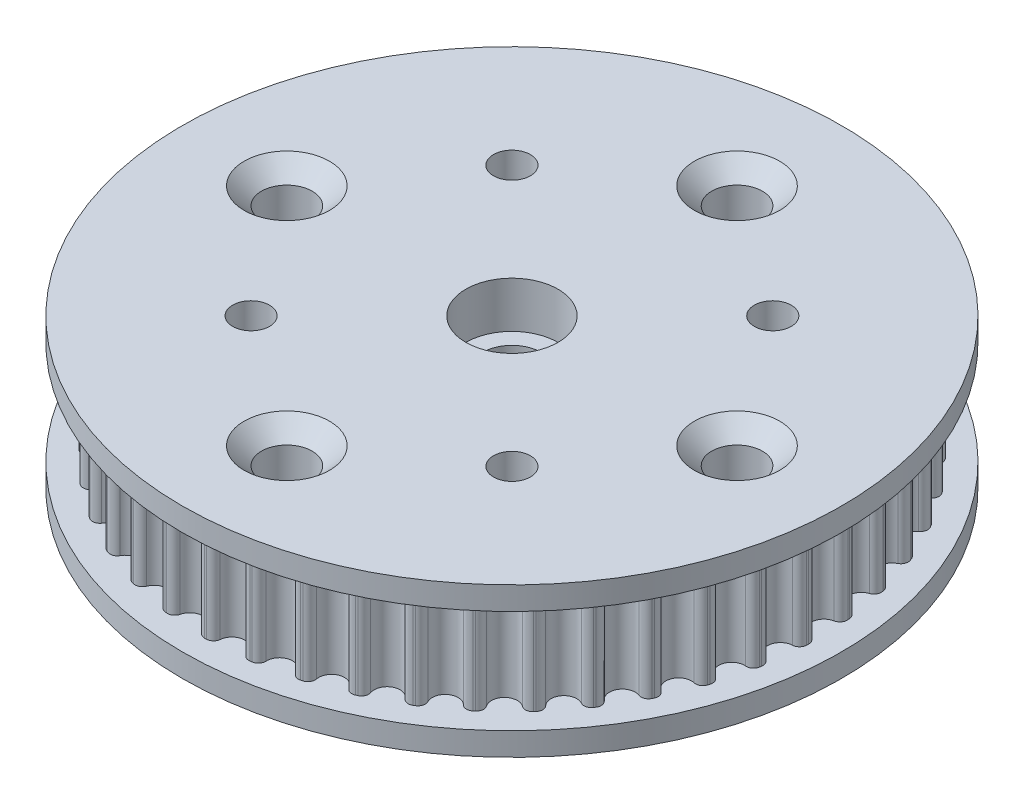
SolidWorks part; units mm, degrees
ref_plane "Front Plane" through (0, 0, 0) normal (0, 0, 1) x (1, 0, 0)
ref_plane "Top Plane" through (0, 0, 0) normal (0, 1, 0) x (1, 0, 0)
ref_plane "Right Plane" through (0, 0, 0) normal (1, 0, 0) x (0, 0, -1)
sketch "Sketch1" plane through (0, 0, 0) normal (0, 1, 0) x (1, 0, 0)
  line L0 (0, 0) -> (0, 21.1048) construction
  line L1 (0, 0) -> (2.8913, 20.5726) construction
  circle A0 centre (0, 0) radius 21.1048 construction
  circle A1 centre (0, 0) radius 19.8848 construction
  circle A2 centre (0, 20.7748) radius 0.89 construction
  circle A5 centre (2.8913, 20.5726) radius 0.89 construction
  arc A6 (0, 19.8848) -> (0.8792, 20.6366) centre (0, 20.7748) ccw
  arc A7 (0.8792, 20.6366) -> (1.4065, 21.0579) centre (1.3731, 20.559) cw
  arc A8 (1.5379, 21.0487) -> (2.0014, 20.5582) centre (1.5015, 20.55) cw
  arc A9 (2.7674, 19.6913) -> (2.0014, 20.5582) centre (2.8913, 20.5726) cw
  arc A10 (1.4065, 21.0579) -> (1.5379, 21.0487) centre (0, 0) cw
  arc A11 (0, 19.8848) -> (2.7674, 19.6913) centre (0, 0) ccw
  dimension "D1" = 42.2096
  dimension "D3" = 1.78
  dimension "D4" = 0.5
  dimension "D2" = 1.22
  dimension "D5" = 8
extrude "Boss-Extrude1" add sketch "Sketch1" along normal mid plane 7.112
ref_axis "Axis1" through (0, 3.3, 0) along (0, -1, 0)
pattern_circular "CirPattern1" count 45 over 360 about axis through (0, 3.3, 0) along (0, -1, 0) of "Boss-Extrude1"
sketch "Sketch2" plane through (0, 0, 0) normal (1, 0, 0) x (0, 0, -1)
  line L0 (-20.6477, 3.556) -> (-21.1047, 3.556) construction
  line L4 (22.6922, 5.1435) -> (2, 5.1435)
  line L5 (22.6922, 5.1435) -> (22.6922, 3.556)
  line L6 (-22.6922, 3.556) -> (22.6922, 3.556) construction
  line L7 (-22.6922, 3.556) -> (-22.6922, 5.1435) construction
  line L8 (-22.6922, 5.1435) -> (22.6922, 5.1435) construction
  line L9 (22.6922, 3.556) -> (22.6922, 5.1435) construction
  line L10 (-22.6922, 3.556) -> (22.6922, 5.1435) construction
  line L11 (-22.6922, 5.1435) -> (22.6922, 3.556) construction
  line L12 (-21.1047, 3.556) -> (-21.1047, -3.556) construction
  line L13 (0, 3.3) -> (0, -3.3) construction
  line L14 (2, 5.1435) -> (2, 3.556)
  line L16 (22.6922, 3.556) -> (2, 3.556)
  line L17 (2, 5.1435) -> (2, 3.556)
  point P0 (0, 4.3498)
  dimension "D1" = 1.5875
  dimension "D2" = 1.5875
  dimension "D3" = 2
revolve "Revolve3" add sketch "Sketch2" angle 360 about axis through (0, 3.3, 0) along (0, -1, 0) region at (0, 4.3497, -12.3461)
mirror "Mirror1" about plane through (0, 0, 0) normal (0, 1, 0) of "Revolve3"
sketch "Sketch3" plane through (0, 3.556, 0) normal (0, 1, 0) x (1, 0, 0)
  line L1 (-8.9803, -8.9803) -> (8.9803, -8.9803) construction
  line L2 (-8.9803, -8.9803) -> (-8.9803, 8.9803) construction
  line L3 (-8.9803, 8.9803) -> (8.9803, 8.9803) construction
  line L4 (8.9803, -8.9803) -> (8.9803, 8.9803) construction
  line L5 (-8.9803, -8.9803) -> (8.9803, 8.9803) construction
  line L6 (-8.9803, 8.9803) -> (8.9803, -8.9803) construction
  circle A0 centre (-15.5, 0) radius 1.7462
  circle A1 centre (0, 0) radius 2
  circle A2 centre (0, 0) radius 2
  circle A3 centre (0, 15.5) radius 1.7462
  circle A4 centre (15.5, 0) radius 1.7462
  circle A5 centre (0, -15.5) radius 1.7462
  circle A6 centre (-8.9803, 8.9803) radius 1.27
  circle A7 centre (8.9803, 8.9803) radius 1.27
  circle A8 centre (8.9803, -8.9803) radius 1.27
  circle A9 centre (-8.9803, -8.9803) radius 1.27
  point P14 (0, 0)
  dimension "D3" = 3.4925
  dimension "D5" = 2.54
  dimension "D2" = 15.5
  dimension "D6" = 25.4
  dimension "D1" = 0
  dimension "D4" = 4
extrude "Cut-Extrude1" cut sketch "Sketch3" against normal through all both and the other way through all
sketch "Sketch4" plane through (0, 5.1435, 0) normal (0, 1, 0) x (1, 0, 0)
  line L0 (-7.9375, 0) -> (7.9375, 0) construction
  line L1 (-7.9375, 3.302) -> (7.9375, 3.302)
  line L2 (-7.9375, -3.302) -> (7.9375, -3.302)
  arc A0 (-7.9375, 3.302) -> (-7.9375, -3.302) centre (-7.9375, 0) ccw
  arc A1 (7.9375, -3.302) -> (7.9375, 3.302) centre (7.9375, 0) ccw
  point P3 (0, 0)
  dimension "D1" = 15.875
  dimension "D2" = 6.604
extrude "Cut-Extrude2" [suppressed] cut sketch "Sketch4" against normal blind 3.175
sketch "Sketch5" [suppressed] plane through (0, 1.9685, 0) normal (0, 1, 0) x (1, 0, 0)
  circle A0 centre (-7.9375, 0) radius 1
  circle A1 centre (7.9375, 0) radius 1
  dimension "D1" = 2
extrude "Cut-Extrude3" [suppressed] cut sketch "Sketch5" against normal through all
ref_axis "Axis2" through (-15.5, -5.1435, 0) along (0, 1, 0)
sketch "Sketch6" plane through (0, 0, 0) normal (0, 0, 1) x (1, 0, 0)
  line L0 (-18.4375, 5.1435) -> (-12.5625, 5.1435) construction
  line L1 (22.6922, 5.1435) -> (-22.6922, 5.1435) construction
  line L2 (-12.5625, 5.1435) -> (-15.5, 2.206)
  line L3 (-15.5, 2.206) -> (-18.4375, 5.1435) construction
  line L4 (-13.7538, 5.1435) -> (-17.2462, 5.1435) construction
  line L5 (-17.2462, 4.8895) -> (-13.7538, 4.8895) construction
  line L6 (-17.2462, 5.1435) -> (-17.2462, -5.1435) construction
  line L7 (-13.7538, -5.1435) -> (-13.7538, 5.1435) construction
  line L8 (-15.5, 2.206) -> (-15.5, 5.1435)
  line L9 (-15.5, 5.1435) -> (-12.5625, 5.1435)
  line L10 (-15.5, -5.1435) -> (-15.5, 5.1435) construction
  point P4 (-15.5, 4.8895)
  point P6 (-15.5, 5.1435)
  dimension "D2" = 5.875
  dimension "D3" = 0.254
revolve "Cut-Revolve2" cut sketch "Sketch6" angle 360 about axis through (-15.5, -5.1435, 0) along (0, 1, 0)
pattern_circular "CirPattern2" count 4 over 360 about axis through (0, 3.3, 0) along (0, -1, 0) of "Cut-Revolve2"
sketch "Sketch7" [suppressed] plane through (0, -5.1435, 0) normal (0, -1, 0) x (-1, 0, 0)
  line L0 (7.9375, 0) -> (-7.9375, 0) construction
  line L1 (7.9375, -2.54) -> (-7.9375, -2.54)
  line L2 (7.9375, 2.54) -> (-7.9375, 2.54)
  arc A0 (7.9375, -2.54) -> (7.9375, 2.54) centre (7.9375, 0) ccw
  arc A1 (-7.9375, 2.54) -> (-7.9375, -2.54) centre (-7.9375, 0) ccw
  point P4 (0, 0)
  dimension "D1" = 5.08
extrude "Cut-Extrude5" [suppressed] cut sketch "Sketch7" against normal offset from surface (2.287 mm away) 8 up to face at (-2.9375, 5.1435, 15.5)
sketch "Sketch8" plane through (0, 5.1435, 0) normal (0, 1, 0) x (1, 0, 0)
  circle A0 centre (0, 0) radius 3.175
  dimension "D1" = 6.35
extrude "Cut-Extrude6" cut sketch "Sketch8" against normal blind 3.175
equation "\"TEETH_NUM\"= 45"
equation "\"TOOTH_PITCH\"= 3mm"
equation "\"PITCH_LINE_OFFSET\"= .015in"
equation "\"DIAMETER_PER_GROOVE\"= .954925mm"
equation "\"PITCH_DIAMETER\"= \"TEETH_NUM\" * \"DIAMETER_PER_GROOVE\""
equation "\"OUTSIDE_DIAMETER\"= \"PITCH_DIAMETER\" - \"PITCH_LINE_OFFSET\" * 2"
equation "\"D1@Sketch1\"=\"OUTSIDE_DIAMETER\""
equation "\"TOOTH_HEIGHT\"= 1.22mm"
equation "\"D2@Sketch1\"=\"TOOTH_HEIGHT\""
equation "\"TOOTH_DIAMETER\"= 1.78mm"
equation "\"INTERNAL_RADIUS\"= .5mm"
equation "\"D3@Sketch1\"=\"TOOTH_DIAMETER\""
equation "\"D5@Sketch1\"=360 / \"TEETH_NUM\""
equation "\"D4@Sketch1\"=\"INTERNAL_RADIUS\""
equation "\"D1@CirPattern1\"=\"TEETH_NUM\""
equation "\"BELT_GAP\"= 7mm"
